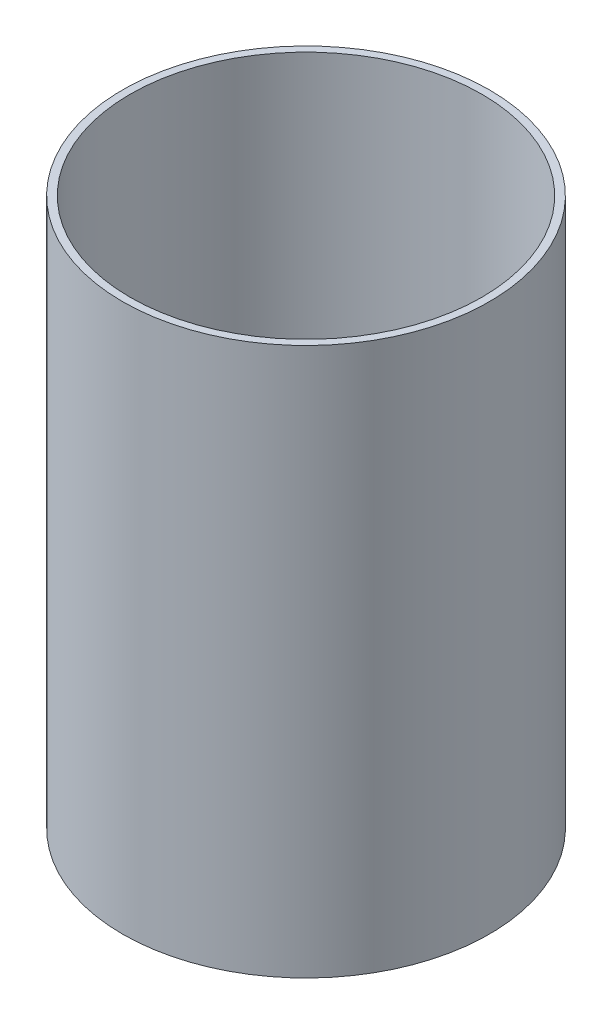
SolidWorks part; units mm, degrees
material "Fonte grise"
ref_plane "Plan de face" through (0, 0, 0) normal (0, 0, 1) x (1, 0, 0)
ref_plane "Plan de dessus" through (0, 0, 0) normal (0, 1, 0) x (1, 0, 0)
ref_plane "Plan de droite" through (0, 0, 0) normal (1, 0, 0) x (0, 0, -1)
sketch "Esquisse1" plane through (0, 0, 0) normal (0, 1, 0) x (1, 0, 0)
  circle A0 centre (0, 0) radius 36.5
  dimension "D1" = 73
extrude "Boss.-Extru.1" add sketch "Esquisse1" along normal blind 109
shell "Coque1" thickness 1.5 removed face at (0, 109, 36.5)
